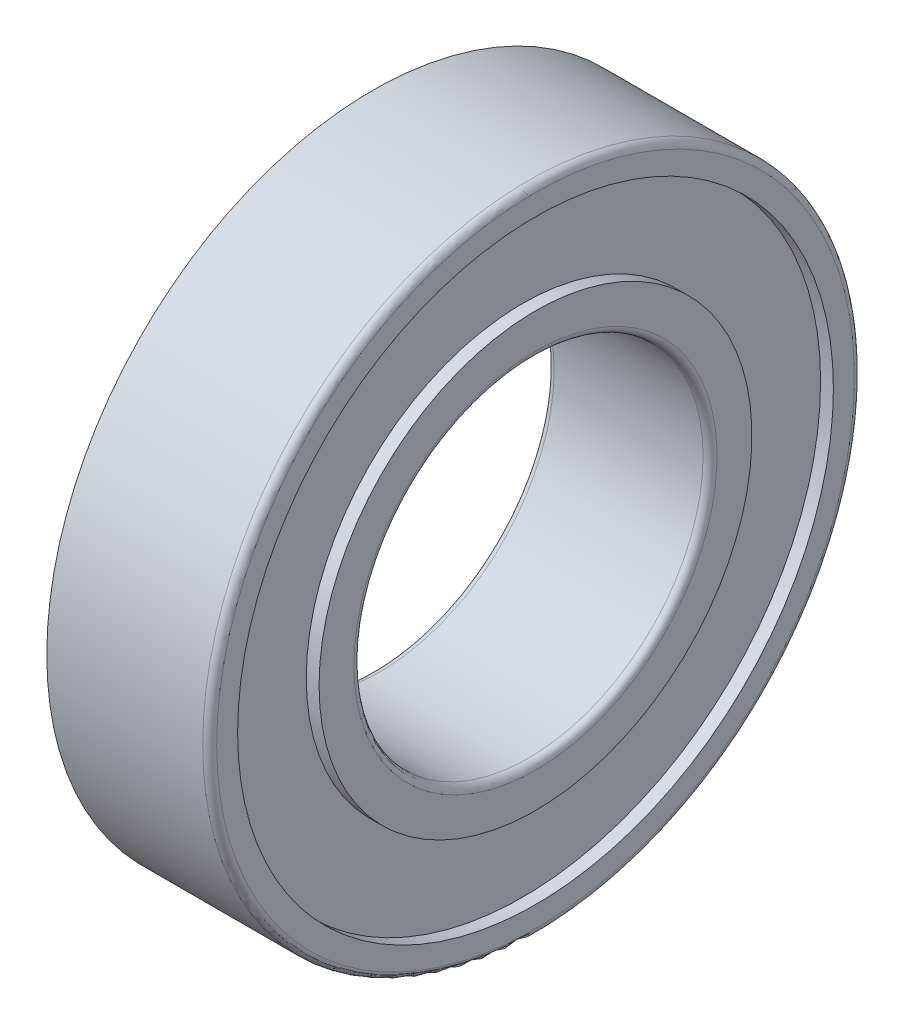
SolidWorks part; units mm, degrees
ref_plane "前视基准面" through (0, 0, 0) normal (0, 0, 1) x (1, 0, 0)
ref_plane "上视基准面" through (0, 0, 0) normal (0, 1, 0) x (1, 0, 0)
ref_plane "右视基准面" through (0, 0, 0) normal (1, 0, 0) x (0, 0, -1)
sketch "草图1" plane through (0, 0, 0) normal (0, 0, 1) x (1, 0, 0)
  line L0 (0, 14) -> (0, 12.8)
  line L1 (0, 12.8) -> (0.55, 12.8)
  line L2 (0.55, 12.8) -> (0.55, 9.3)
  line L3 (0.55, 9.3) -> (0, 9.3)
  line L4 (0, 9.3) -> (0, 7.8)
  line L5 (0.3, 7.5) -> (6.7, 7.5)
  line L6 (7, 7.8) -> (7, 9.3)
  line L7 (7, 9.3) -> (6.45, 9.3)
  line L8 (6.45, 9.3) -> (6.45, 12.8)
  line L9 (6.45, 12.8) -> (7, 12.8)
  line L10 (7, 12.8) -> (7, 13.7)
  line L11 (6.7, 14) -> (0, 14)
  line L12 (7, 0) -> (0, 0) construction
  arc A0 (0, 7.8) -> (0.3, 7.5) centre (0.3, 7.8) ccw
  arc A1 (6.7, 7.5) -> (7, 7.8) centre (6.7, 7.8) ccw
  arc A2 (7, 13.7) -> (6.7, 14) centre (6.7, 13.7) ccw
revolve "旋转1" add sketch "草图1" angle 360 about L12 reverse direction yes
ref_plane "基准面4" through (1.3, 0, 0) normal (1, 0, 0) x (0, 0, -1)
ref_plane "基准面5" through (3.5, 0, 0) normal (1, 0, 0) x (0, 0, -1)
ref_plane "to_ring XY" through (1.3, 0, 0) normal (1, 0, 0) x (0, 0, -1)
ref_plane "to_ring XZ" through (0, 0, 0) normal (0, -1, 0) x (-1, 0, 0)
ref_plane "to_ring YZ" through (0, 0, 0) normal (0, 0, -1) x (-1, 0, 0)
ref_axis "to_ring X" through (1.3, 0, 80.9) along (0, 0, -1)
ref_axis "to_ring Y" through (1.3, -50, 0) along (0, 1, 0)
ref_axis "to_ring Z" through (80.9, 0, 0) along (-1, 0, 0)
sketch3d "to_ring"
  point P0 (1.3, 0, 0)
ref_plane "to_housing XY" through (0, 0, 0) normal (1, 0, 0) x (0, 0, -1)
ref_plane "to_housing XZ" through (0, 0, 0) normal (0, -1, 0) x (-1, 0, 0)
ref_plane "to_housing YZ" through (0, 0, 0) normal (0, 0, -1) x (-1, 0, 0)
ref_axis "to_housing X" through (0, 0, 80.9) along (0, 0, -1)
ref_axis "to_housing Y" through (0, -50, 0) along (0, 1, 0)
ref_axis "to_housing Z" through (80.9, 0, 0) along (-1, 0, 0)
sketch3d "to_housing"
  point P0 (0, 0, 0)
ref_plane "center_point XY" through (3.5, 0, 0) normal (1, 0, 0) x (0, 0, -1)
ref_plane "center_point XZ" through (0, 0, 0) normal (0, -1, 0) x (-1, 0, 0)
ref_plane "center_point YZ" through (0, 0, 0) normal (0, 0, -1) x (-1, 0, 0)
ref_axis "center_point X" through (3.5, 0, 80.9) along (0, 0, -1)
ref_axis "center_point Y" through (3.5, -50, 0) along (0, 1, 0)
ref_axis "center_point Z" through (80.9, 0, 0) along (-1, 0, 0)
sketch3d "center_point"
  point P0 (3.5, 0, 0)
